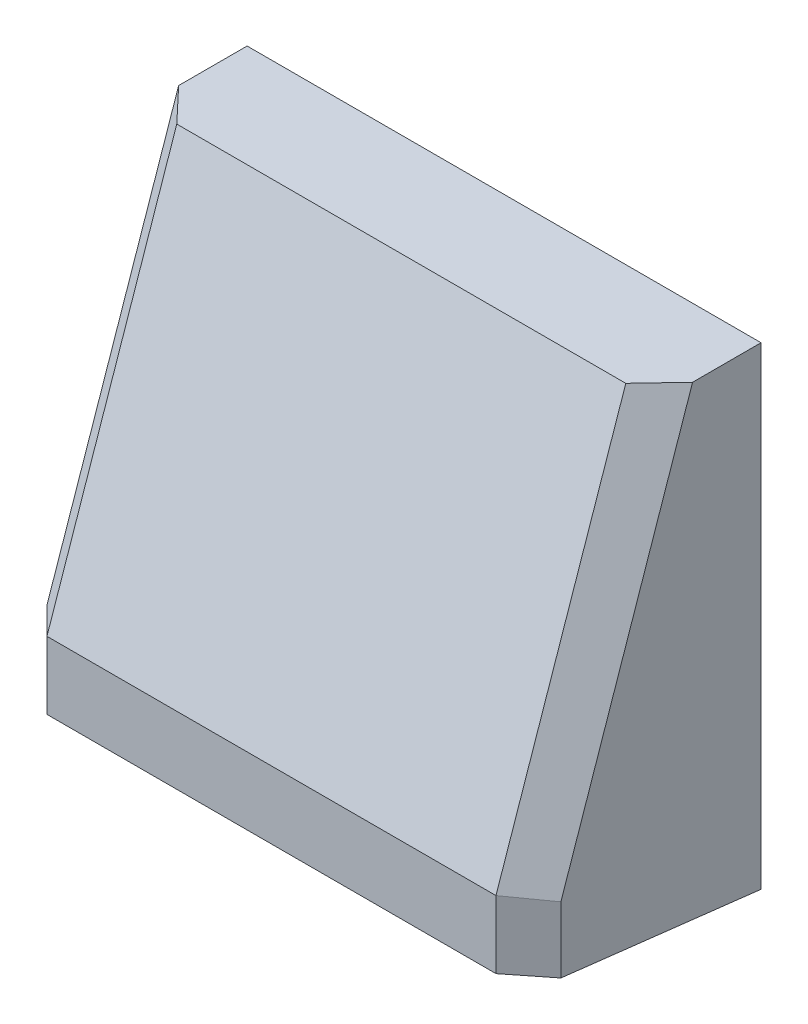
SolidWorks part; units mm, degrees
ref_plane "Front Plane" through (0, 0, 0) normal (0, 0, 1) x (1, 0, 0)
ref_plane "Top Plane" through (0, 0, 0) normal (0, 1, 0) x (1, 0, 0)
ref_plane "Right Plane" through (0, 0, 0) normal (1, 0, 0) x (0, 0, -1)
sketch "Sloped Cover Outer Side Profile" plane through (0, 0, 0) normal (1, 0, 0) x (0, 0, -1)
  line L0 (-22, 25) -> (-22, 200)
  line L1 (-22, 200) -> (-60, 200)
  line L2 (-60, 200) -> (-108, 60)
  line L3 (-108, 60) -> (-108, 35)
  line L4 (-108, 35) -> (-22, 25)
extrude "Sloped Cover Blank" add sketch "Sloped Cover Outer Side Profile" along normal blind 95 and the other way blind 95 separate body
sketch "Open Bottom Cover Cavity Profile" plane through (0, 0, 0) normal (1, 0, 0) x (0, 0, -1)
  line L0 (-18, 23) -> (-18, 193)
  line L1 (-18, 193) -> (-48, 193)
  line L2 (-48, 193) -> (-96, 60)
  line L3 (-96, 60) -> (-96, 33.6047)
  line L4 (-108, 35) -> (-22, 25) construction
  line L5 (-96, 33.6047) -> (-18, 23)
extrude "Open Bottom and Front Cover Cavity" cut sketch "Open Bottom Cover Cavity Profile" against normal blind 80 and the other way blind 80
chamfer "12 mm Full-Length Shape-Defining Roof Chamfers" distance 12 angle 45 4 edges at (95, 130, 84) (95, 47.5, 108) (-95, 130, 84) (-95, 47.5, 108) tangent propagation no
